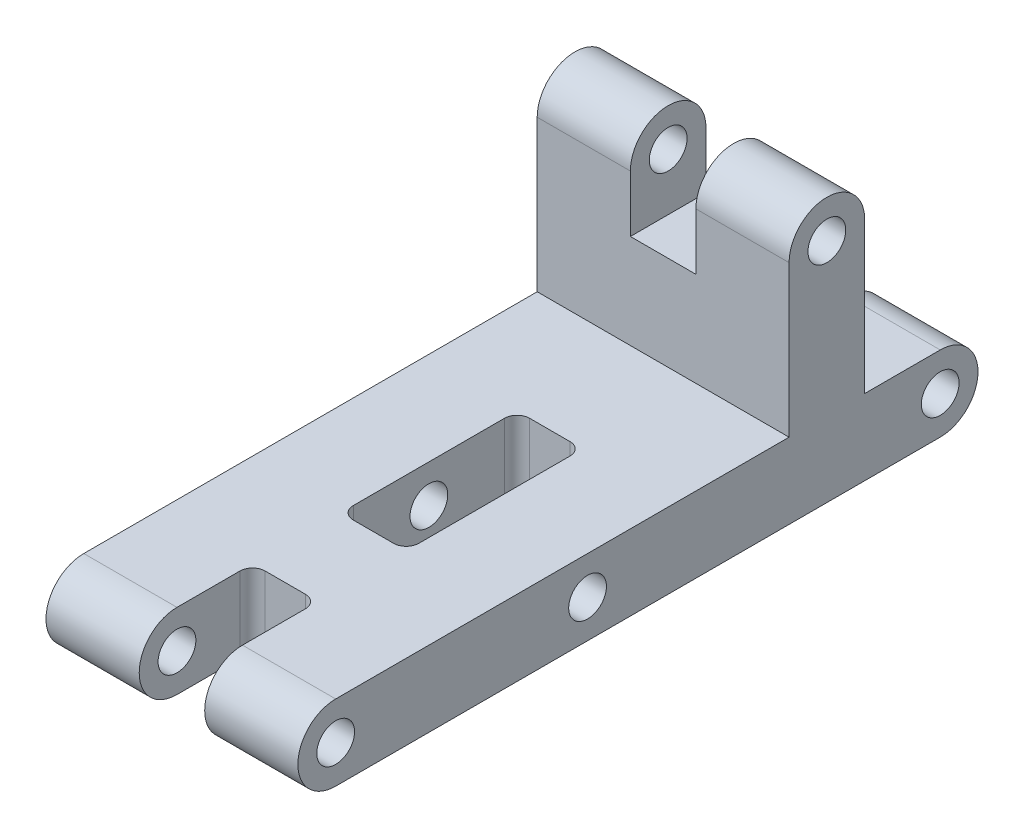
SolidWorks part; units mm, degrees
ref_plane "Alzado" through (0, 0, 0) normal (0, 0, 1) x (1, 0, 0)
ref_plane "Planta" through (0, 0, 0) normal (0, 1, 0) x (1, 0, 0)
ref_plane "Vista lateral" through (0, 0, 0) normal (1, 0, 0) x (0, 0, -1)
sketch "Croquis1" plane through (0, 0, 0) normal (1, 0, 0) x (0, 0, -1)
  line L0 (-14, 0) -> (14, 0) construction
  line L1 (-14, 3) -> (2, 3)
  line L2 (-14, -3) -> (14, -3)
  line L3 (8, 3) -> (14, 3)
  line L5 (2, 3) -> (2, 15)
  line L6 (2, 15) -> (8, 15) construction
  line L7 (8, 3) -> (8, 15)
  line L8 (-14, 3) -> (-34, 3)
  line L9 (-14, -3) -> (-34, -3)
  line L10 (-34, 3) -> (-34, -3) construction
  arc A0 (-14, 3) -> (-14, -3) centre (-14, 0) ccw construction
  arc A1 (14, -3) -> (14, 3) centre (14, 0) ccw
  circle A2 centre (14, 0) radius 1.5
  arc A3 (8, 15) -> (2, 15) centre (5, 15) ccw
  circle A4 centre (5, 15) radius 1.5
  circle A5 centre (-14, 0) radius 1.5
  arc A6 (-34, 3) -> (-34, -3) centre (-34, 0) ccw
  circle A7 centre (-34, 0) radius 1.5
  point P3 (0, 0)
  dimension "D2" = 3
  dimension "D3" = 3
  dimension "D4" = 3
  dimension "D7" = 20
  dimension "D1" = 28
  dimension "D5" = 6
  dimension "D6" = 12
extrude "Saliente-Extruir1" add sketch "Croquis1" along normal mid plane 20
sketch "Croquis2" plane through (0, 0, 0) normal (1, 0, 0) x (0, 0, -1)
  line L0 (2, 15) -> (2, 3) construction
  line L1 (2, 10.5) -> (8, 10.5)
  line L2 (2, 10.5) -> (2, 18)
  line L3 (2, 18) -> (8, 18)
  line L4 (8, 10.5) -> (8, 18)
  line L5 (8, 3) -> (8, 15) construction
  line L6 (2, 3) -> (-34, 3) construction
  line L7 (-7, 3) -> (-21, 3)
  line L8 (-7, 3) -> (-7, -3)
  line L9 (-7, -3) -> (-21, -3)
  line L10 (-21, 3) -> (-21, -3)
  line L11 (-34, -3) -> (14, -3) construction
  line L12 (14, 3) -> (8, 3) construction
  line L13 (8, 3) -> (17, 3)
  line L14 (8, 3) -> (8, -3)
  line L15 (8, -3) -> (17, -3)
  line L16 (17, 3) -> (17, -3)
  line L17 (2, 3) -> (-34, 3) construction
  line L18 (-28, 3) -> (-37, 3)
  line L19 (-28, 3) -> (-28, -3)
  line L20 (-28, -3) -> (-37, -3)
  line L21 (-37, 3) -> (-37, -3)
  line L22 (-34, -3) -> (14, -3) construction
  arc A0 (8, 15) -> (2, 15) centre (5, 15) ccw construction
  arc A2 (14, -3) -> (14, 3) centre (14, 0) ccw construction
  circle A4 centre (-14, 0) radius 1.5 construction
  arc A5 (-34, 3) -> (-34, -3) centre (-34, 0) ccw construction
  dimension "D5" = 9
  dimension "D1" = 7.5
  dimension "D2" = 7
  dimension "D3" = 9
  dimension "D4" = 7
extrude "Cortar-Extruir1" cut sketch "Croquis2" against normal mid plane 5.2
fillet "Redondeo1" radius 1 8 edges at (2.6, 0, 7) (2.6, 0, 21) (-2.6, 0, 7) (-2.6, 0, 21) (2.6, 0, 28) (-2.6, 0, 28) (2.6, 0, -8) (-2.6, 0, -8)
